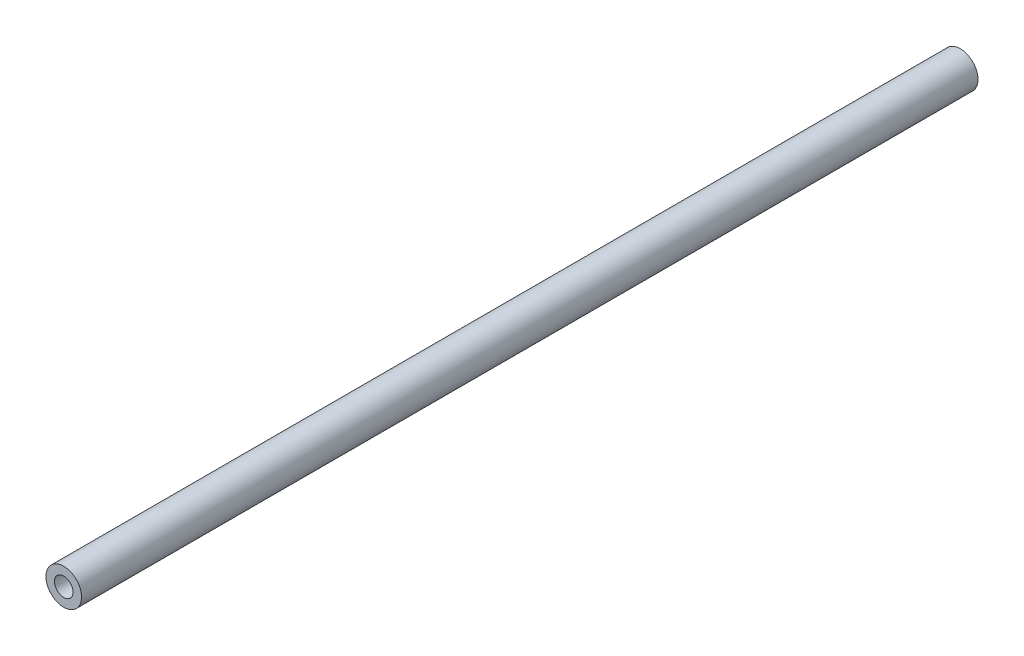
SolidWorks part; units mm, degrees
material "6061-T6 (SS)"
ref_plane "Front Plane" through (0, 0, 0) normal (0, 0, 1) x (1, 0, 0)
ref_plane "Top Plane" through (0, 0, 0) normal (0, 1, 0) x (1, 0, 0)
ref_plane "Right Plane" through (0, 0, 0) normal (1, 0, 0) x (0, 0, -1)
sketch "Sketch1" plane through (0, 0, 0) normal (0, 0, 1) x (1, 0, 0)
  circle A0 centre (0, 0) radius 2.4892
  circle A1 centre (0, 0) radius 4.7625
  dimension "D1" = 4.9784
  dimension "D2" = 9.525
extrude "Boss-Extrude1" add sketch "Sketch1" along normal mid plane 240.03
